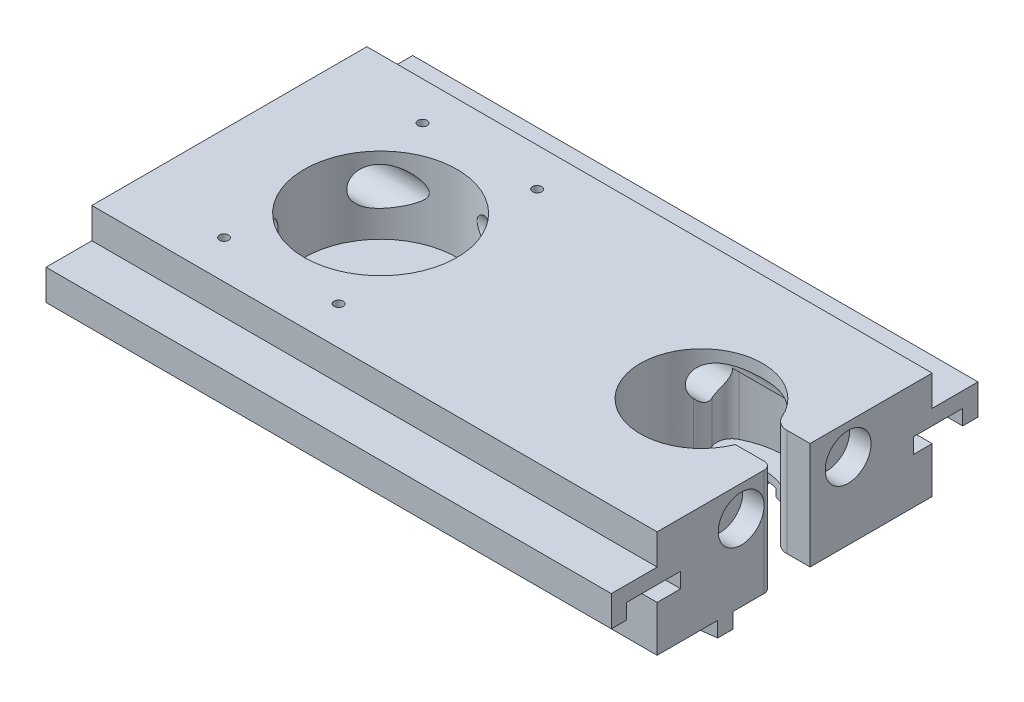
SolidWorks part; units mm, degrees
ref_plane "Front Plane" through (0, 0, 0) normal (0, 0, 1) x (1, 0, 0)
ref_plane "Top Plane" through (0, 0, 0) normal (0, 1, 0) x (1, 0, 0)
ref_plane "Right Plane" through (0, 0, 0) normal (1, 0, 0) x (0, 0, -1)
sketch "Sketch2" plane through (0, 0, 0) normal (0, 1, 0) x (1, 0, 0)
  line L0 (61, 90) -> (61, -90)
  line L1 (61, -90) -> (-309, -90)
  line L2 (-309, -90) -> (-309, 90)
  line L3 (-309, 90) -> (61, 90)
  line L4 (-59, 90) -> (-59, -90)
  circle A0 centre (0, 0) radius 40
  dimension "D6" = 80
  dimension "D1" = 61
  dimension "D2" = 90
  dimension "D3" = 90
  dimension "D4" = 120
  dimension "D5" = 250
extrude "Boss-Extrude1" add sketch "Sketch2" along normal blind 80 contours L3 L4 L1 L0 A0 | L4 L3 L2 L1 region at (58.8367, 0, 0) region at (-184, 0, 0)
sketch "Sketch4" plane through (-309, 0, 0) normal (-1, 0, 0) x (0, 0, 1)
  line L0 (90, 80) -> (-90, 80) construction
  line L1 (0, 80) -> (0, 0) construction
  circle A0 centre (-35, 60) radius 12.5
  circle A2 centre (35, 60) radius 12.5
  dimension "D1" = 25
  dimension "D2" = 35
  dimension "D3" = 20
extrude "Cut-Extrude1" cut sketch "Sketch4" against normal offset from surface (350 mm away) 20 up to face at (61, 40, 0)
sketch "Sketch9" plane through (61, 0, 0) normal (1, 0, 0) x (0, 0, -1)
  circle A0 centre (35, 60) radius 4.5
  circle A1 centre (-35, 60) radius 4.5
  dimension "D1" = 9
  dimension "D2" = 9
extrude "Cut-Extrude5" cut sketch "Sketch9" against normal blind 24
sketch "Sketch10" plane through (61, 0, 0) normal (1, 0, 0) x (0, 0, -1)
  circle A0 centre (-35, 60) radius 15
  circle A1 centre (35, 60) radius 15
  circle M3 centre (35, 60) radius 4.5
  circle M4 centre (-35, 60) radius 4.5
  dimension "D1" = 30
extrude "Cut-Extrude6" cut sketch "Sketch10" against normal blind 14 contours A0 M4 | A1 M3 region at (61, 60, 49.5757) region at (61, 60, -20.4243)
sketch "Sketch12" plane through (0, 0, 0) normal (0, -1, 0) x (1, 0, 0)
  line L0 (-309, 90) -> (-309, -90) construction
  line L1 (-309, -103.9431) -> (-309, -90)
  line L2 (-309, -90) -> (61, -90) construction
  line L3 (-309, -90) -> (61, -90)
  line L4 (61, -90) -> (61, 90) construction
  line L5 (61, -90) -> (61, 40.2615)
  line L8 (-309, -88.1909) -> (-309, 90)
  line L9 (-309, 90) -> (61, 90)
  line L10 (61, 90) -> (61, 50.3798)
  circle A0 centre (0, -350) radius 350 construction
  arc A1 (61, 40.2615) -> (-309, -103.9431) centre (0, -350) ccw
  arc A2 (61, 50.3798) -> (-309, -88.1909) centre (0, -350) ccw
  circle A3 centre (0, -350) radius 395 construction
  circle A4 centre (0, -350) radius 405 construction
  circle M1 centre (0, 0) radius 40
  line M2 (61, -90) -> (61, 90)
  line M4 (-309, 90) -> (-309, -90)
  line M8 (-309, -90) -> (61, -90)
  dimension "D1" = 700
  dimension "D2" = 45
  dimension "D3" = 10
extrude "Cut-Extrude8" cut sketch "Sketch12" against normal blind 10 contours A1 M2 M4 M8 M1 | L10 A2 L8 L9 region at (-95.0829, 0, -37.712)
ref_plane "Plane1" through (0, 20, 0) normal (0, -1, 0) x (-1, 0, 0)
sketch "Sketch18" plane through (0, 20, 0) normal (0, -1, 0) x (-1, 0, 0)
  line L0 (-35, 42.4264) -> (35, -42.4264)
  line L1 (35, 42.4264) -> (-35, -42.4264)
  arc A0 (-35, -42.4264) -> (35, -42.4264) centre (0, 0) ccw
  arc A1 (25.4545, 30.8556) -> (-25.4545, 30.8556) centre (0, 0) ccw construction
  arc A3 (-25.4545, -30.8556) -> (25.4545, -30.8556) centre (0, 0) ccw construction
  arc A5 (35, 42.4264) -> (-35, 42.4264) centre (0, 0) ccw
  dimension "D1" = 110
  dimension "D2" = 35
  dimension "D3" = 35
extrude "Cut-Extrude16" cut sketch "Sketch18" against normal blind 40 contours L1 A0 L0 | L1 A5 L0 region at (0, 20, -33.8275) region at (0, 20, 33.8275)
fillet "Fillet5" radius 10 4 edges at (-35, 34.9726, 42.4264) (35, 34.9726, 42.4264) (-35, 34.9726, -42.4264) (35, 34.9726, -42.4264)
fillet "Fillet6" radius 10 4 edges at (-25.4545, 34.1035, 30.8556) (25.4545, 34.1035, 30.8556) (25.4545, 34.1035, -30.8556) (-25.4545, 34.1035, -30.8556)
sketch "Sketch19" plane through (0, 10, 0) normal (0, -1, 0) x (1, 0, 0)
  line L2 (-297.3634, -90) -> (61, -90) construction
  line L3 (0, 0) -> (10, 0)
  line L6 (0, 0) -> (0, -90)
  line L7 (0, -90) -> (10, -90)
  line L8 (10, 0) -> (10, -90)
  dimension "D1" = 10
extrude "Cut-Extrude17" cut sketch "Sketch19" against normal blind 5
sketch "Sketch21" plane through (0, 10, 0) normal (0, -1, 0) x (1, 0, 0)
  line L0 (61, -90) -> (61, 40.2615) construction
  line L1 (61, -10.1064) -> (61, 14.8938)
  arc A0 (61, -0.1063) -> (40, -0.0457) centre (0, -17500) ccw construction
  arc A1 (61, 14.8938) -> (37.0969, 14.9607) centre (0, -17500) ccw
  arc A2 (61, -10.1064) -> (38.7187, -10.0429) centre (0, -17500) ccw
  arc A3 (10, -38.7298) -> (0, -40) centre (0, 0) ccw construction
  arc A4 (38.7187, -10.0429) -> (37.0969, 14.9607) centre (0, 0) ccw
  circle A5 centre (0, -17500) radius 17490 construction
  circle A6 centre (0, -17500) radius 17500 construction
  circle A7 centre (0, -17500) radius 17515 construction
  dimension "D1" = 35000
  dimension "D2" = 15
  dimension "D3" = 10
extrude "Cut-Extrude18" cut sketch "Sketch21" against normal through all
fillet "Fillet7" radius 5 1 edges at (61, 45, 14.8938)
fillet "Fillet8" radius 10 1 edges at (38.7187, 45, -10.0429)
sketch "Sketch22" plane through (-309, 0, 0) normal (-1, 0, 0) x (0, 0, 1)
  circle A0 centre (-35, 60) radius 15
  circle A1 centre (35, 60) radius 15
  dimension "D1" = 30
  dimension "D2" = 30
extrude "Cut-Extrude19" cut sketch "Sketch22" against normal blind 14
sketch "Sketch23" plane through (0, 80, 0) normal (0, 1, 0) x (1, 0, 0)
  circle A0 centre (-210, 0) radius 50
  dimension "D1" = 100
  dimension "D2" = 210
extrude "Cut-Extrude20" cut sketch "Sketch23" against normal blind 50
sketch "Sketch24" plane through (0, 80, 0) normal (0, 1, 0) x (1, 0, 0)
  line L0 (-210, 0) -> (-135, 0) construction
  line L1 (-210, 0) -> (-172.5, 64.9519) construction
  line L2 (-210, 75) -> (-210, -75) construction
  circle A0 centre (-210, 0) radius 75 construction
  circle A1 centre (-172.5, 64.9519) radius 3
  circle A2 centre (-247.5, 64.9519) radius 3
  circle A3 centre (-172.5, -64.9519) radius 3
  circle A4 centre (-247.5, -64.9519) radius 3
  dimension "D1" = 150
  dimension "D2" = 6
  dimension "D3" = 60
extrude "Cut-Extrude21" cut sketch "Sketch24" against normal through all
sketch "Sketch27" plane through (-309, 0, 0) normal (-1, 0, 0) x (0, 0, 1)
  line L0 (90, 80) -> (90, 10) construction
  line L1 (105.4153, 50) -> (74.5847, 50)
  line L2 (105.4153, 50) -> (105.4153, 40)
  line L3 (105.4153, 40) -> (74.5847, 40)
  line L4 (74.5847, 50) -> (74.5847, 40)
  line L5 (105.4153, 50) -> (74.5847, 40) construction
  line L6 (105.4153, 40) -> (74.5847, 50) construction
  line L7 (-90, 80) -> (-90, 10) construction
  line L8 (-102.3475, 50) -> (-77.6525, 50)
  line L9 (-102.3475, 50) -> (-102.3475, 40)
  line L10 (-102.3475, 40) -> (-77.6525, 40)
  line L11 (-77.6525, 50) -> (-77.6525, 40)
  line L12 (-102.3475, 50) -> (-77.6525, 40) construction
  line L13 (-102.3475, 40) -> (-77.6525, 50) construction
  point P0 (90, 45)
  point P9 (-90, 45)
  dimension "D1" = 10
  dimension "D2" = 10
extrude "Cut-Extrude22" cut sketch "Sketch27" against normal through all both and the other way through all
sketch "Sketch28" plane through (-309, 0, 0) normal (-1, 0, 0) x (0, 0, 1)
  line L0 (-90, 80) -> (-90, 50) construction
  line L1 (-90, 50) -> (-110, 50)
  line L2 (-90, 50) -> (-90, 60)
  line L3 (-90, 60) -> (-120, 60)
  line L4 (-120, 50) -> (-120, 60)
  line L5 (-120, 50) -> (-120, 40)
  line L6 (90, 50) -> (110, 50)
  line L7 (90, 50) -> (90, 60)
  line L8 (90, 60) -> (120, 60)
  line L9 (120, 50) -> (120, 60)
  line L10 (-120, 40) -> (-110, 40)
  line L11 (-110, 40) -> (-110, 50)
  line L12 (120, 50) -> (120, 40)
  line L13 (120, 40) -> (110, 40)
  line L14 (110, 40) -> (110, 50)
  dimension "D1" = 10
  dimension "D2" = 10
  dimension "D3" = 30
  dimension "D4" = 30
  dimension "D5" = 10
  dimension "D6" = 10
  dimension "D7" = 10
  dimension "D8" = 10
extrude "Boss-Extrude2" add sketch "Sketch28" against normal through all
